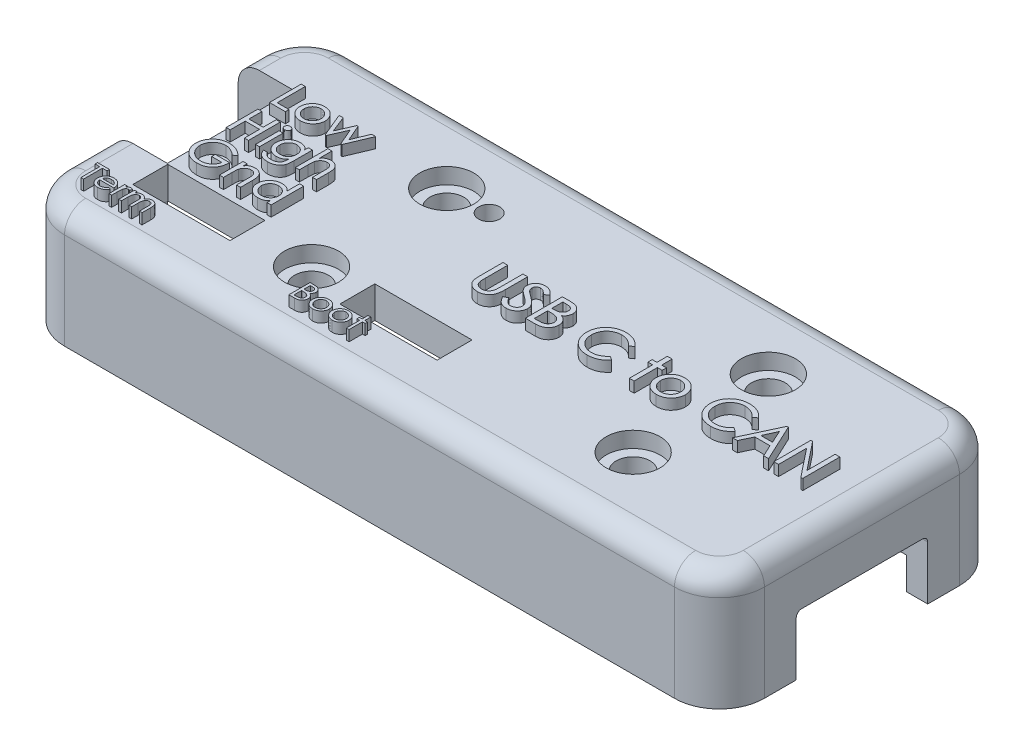
SolidWorks part; units mm, degrees
ref_plane "Front Plane" through (0, 0, 0) normal (0, 0, 1) x (1, 0, 0)
ref_plane "Top Plane" through (0, 0, 0) normal (0, 1, 0) x (1, 0, 0)
ref_plane "Right Plane" through (0, 0, 0) normal (1, 0, 0) x (0, 0, -1)
sketch "Sketch1" plane through (0, 0, 0) normal (0, 1, 0) x (1, 0, 0)
  line L0 (-0.25, 0.25) -> (55.35, 0.25)
  line L1 (0, 0) -> (55.1, 0)
  line L2 (0, 0) -> (0, -15.92)
  line L3 (0, -15.92) -> (55.1, -15.92)
  line L4 (55.1, 0) -> (55.1, -15.92)
  line L5 (55.35, 0.25) -> (55.35, -16.17)
  line L6 (-0.25, -16.17) -> (55.35, -16.17)
  line L7 (-0.25, 0.25) -> (-0.25, -16.17)
  line L8 (-1.25, 3.25) -> (56.35, 3.25)
  line L9 (58.35, 1.25) -> (58.35, -17.17)
  line L10 (-1.25, -19.17) -> (56.35, -19.17)
  line L11 (-3.25, 1.25) -> (-3.25, -17.17)
  line L12 (-3.25, -19.17) -> (58.35, -19.17) construction
  line L13 (-3.25, 3.25) -> (-3.25, -19.17) construction
  line L14 (58.35, 3.25) -> (58.35, -19.17) construction
  line L15 (-3.25, 3.25) -> (58.35, 3.25) construction
  line L20 (-1.25, -19.42) -> (56.35, -19.42)
  line L21 (58.6, 1.25) -> (58.6, -17.17)
  line L22 (-1.25, 3.5) -> (56.35, 3.5)
  line L23 (-3.5, 1.25) -> (-3.5, -17.17)
  line L24 (-1.25, -21.42) -> (56.35, -21.42)
  line L25 (60.6, 1.25) -> (60.6, -17.17)
  line L26 (-1.25, 5.5) -> (56.35, 5.5)
  line L27 (-5.5, 1.25) -> (-5.5, -17.17)
  circle A0 centre (45.375, -1.575) radius 1.6
  circle A1 centre (45.375, -14.345) radius 1.6
  circle A2 centre (15.005, -1.575) radius 1.6
  circle A3 centre (15.005, -14.345) radius 1.6
  arc A8 (-1.25, -19.17) -> (-3.25, -17.17) centre (-1.25, -17.17) cw
  arc A9 (58.35, -17.17) -> (56.35, -19.17) centre (56.35, -17.17) cw
  arc A10 (56.35, 3.25) -> (58.35, 1.25) centre (56.35, 1.25) cw
  arc A11 (-1.25, 3.25) -> (-3.25, 1.25) centre (-1.25, 1.25) ccw
  arc A16 (58.6, -17.17) -> (56.35, -19.42) centre (56.35, -17.17) cw
  arc A17 (56.35, 3.5) -> (58.6, 1.25) centre (56.35, 1.25) cw
  arc A18 (-1.25, 3.5) -> (-3.5, 1.25) centre (-1.25, 1.25) ccw
  arc A19 (-1.25, -19.42) -> (-3.5, -17.17) centre (-1.25, -17.17) cw
  arc A20 (60.6, -17.17) -> (56.35, -21.42) centre (56.35, -17.17) cw
  arc A21 (56.35, 5.5) -> (60.6, 1.25) centre (56.35, 1.25) cw
  arc A22 (-1.25, 5.5) -> (-5.5, 1.25) centre (-1.25, 1.25) ccw
  arc A23 (-1.25, -21.42) -> (-5.5, -17.17) centre (-1.25, -17.17) cw
  dimension "D8" = 3.2
  dimension "D9" = 3.2
  dimension "D10" = 3.2
  dimension "D11" = 3.2
  dimension "D15" = 2
  dimension "D1" = 15.92
  dimension "D2" = 55.1
  dimension "D4" = 9.725
  dimension "D5" = 30.37
  dimension "D6" = 12.77
  dimension "D7" = 1.575
  dimension "D3" = 0.25
  dimension "D14" = 3
  dimension "D16" = 0.25
  dimension "D17" = 2
extrude "Boss-Extrude4" add sketch "Sketch1" against normal blind 3 contours A23 L24 A20 L25 A21 L26 A22 L27 L20 A19 L23 A18 L22 A17 L21 A16 region at (-3.7505, 0, 19.6705)
extrude "Boss-Extrude5" add sketch "Sketch1<8>" along normal blind 5.1 contours A23 L24 A20 L25 A21 L26 A22 L27 L20 A19 L23 A18 L22 A17 L21 A16 | A19 L20 A16 L21 A17 L22 A18 L23 A11 L8 A10 L9 A9 L10 A8 L11 | L8 A11 L11 A8 L10 A9 L9 A10 L6 L7 L0 L5 region at (27.55, 0, -2.5945) region at (-2.7942, 0, 18.7142) region at (-3.7505, 0, 19.6705)
sketch "Sketch1<8>" plane through (0, 0, 0) normal (0, 1, 0) x (1, 0, 0) same geometry as "Sketch1"
extrude "Boss-Extrude6" add sketch "Sketch1<9>" along normal blind 3 from surface contours A20 L24 A23 L27 A22 L26 A21 L25 starting at face at (27.55, 5.1, 7.96)
sketch "Sketch1<9>" plane through (0, 0, 0) normal (0, 1, 0) x (1, 0, 0) same geometry as "Sketch1"
sketch "Sketch5" plane through (-5.5, 0, 0) normal (-1, 0, 0) x (0, 0, 1)
  line L0 (-1.25, -3) -> (-1.25, 8.1) construction
  line L1 (0.77, 8.1) -> (12.71, 8.1)
  line L2 (0.77, 8.1) -> (0.77, -3.76)
  line L3 (0.77, -3.76) -> (12.71, -3.76)
  line L4 (12.71, 8.1) -> (12.71, -3.76)
  line L5 (17.17, 8.1) -> (-1.25, 8.1) construction
  dimension "D1" = 2.02
  dimension "D2" = 11.94
  dimension "D3" = 11.86
  dimension "D4" = 0
extrude "Cut-Extrude4" cut sketch "Sketch5" against normal up to surface (5.25 mm away) up to face at (-0.25, 2.55, 7.96)
extrude "Cut-Extrude6" cut sketch "Sketch1<10>" along normal up to surface (8.1 mm away) contours L1 A0 | L1 A0 | L1 A2 | L3 A3 | L3 A3 | L3 A1 | L3 A1 | A2 region at (15.005, 0, 1.5769) region at (15.005, 0, 14.3431) region at (15.005, 0, 15.93) region at (45.375, 0, -0.01) region at (45.375, 0, 1.5769) region at (45.375, 0, 14.3431) region at (45.375, 0, 15.93) up to face at (17.4083, 8.1, 7.5533)
sketch "Sketch1<10>" plane through (0, 0, 0) normal (0, 1, 0) x (1, 0, 0) same geometry as "Sketch1"
sketch "Sketch6" plane through (0, 8.1, 0) normal (0, 1, 0) x (1, 0, 0)
  circle A0 centre (45.375, -14.345) radius 2.55
  circle A1 centre (45.375, -1.575) radius 2.55
  circle A2 centre (15.005, -1.575) radius 2.55
  circle A3 centre (15.005, -14.345) radius 2.55
  dimension "D1" = 5.1
  dimension "D2" = 5.1
  dimension "D3" = 5.1
  dimension "D4" = 5.1
extrude "Cut-Extrude7" cut sketch "Sketch6" against normal blind 1.5
sketch "Sketch9" plane through (0, 5.1, 0) normal (0, -1, 0) x (1, 0, 0)
  line L0 (-0.25, 16.17) -> (55.35, 16.17) construction
  line L1 (9.03, 12.77) -> (-0.15, 12.77)
  line L2 (9.03, 12.77) -> (9.03, 16.07)
  line L3 (9.03, 16.07) -> (-0.15, 16.07)
  line L4 (-0.15, 12.77) -> (-0.15, 16.07)
  line L5 (-0.25, 12.71) -> (-0.25, 16.17) construction
  line L7 (19.405, 12.77) -> (28.585, 12.77)
  line L8 (19.405, 12.77) -> (19.405, 16.07)
  line L9 (19.405, 16.07) -> (28.585, 16.07)
  line L10 (28.585, 12.77) -> (28.585, 16.07)
  circle A0 centre (15.005, 14.345) radius 1.6 construction
  dimension "D1" = 9.18
  dimension "D2" = 0.1
  dimension "D3" = 0.1
  dimension "D4" = 3.3
  dimension "D5" = 9.18
  dimension "D6" = 4.4
extrude "Cut-Extrude14" cut sketch "Sketch9" against normal blind 4
fillet "Fillet1" radius 2 9 edges at (-5.5, 8.1, 14.94) (-4.2552, 8.1, 20.1752) (27.55, 8.1, 21.42) (59.3552, 8.1, 20.1752) (60.6, 8.1, 7.96) (59.3552, 8.1, -4.2552) (-5.5, 8.1, -0.24) (-4.2552, 8.1, -4.2552) (27.55, 8.1, -5.5)
sketch "Sketch10" plane through (60.6, 0, 0) normal (1, 0, 0) x (0, 0, -1)
  line L1 (-13.6679, 2.57) -> (-2.2479, 2.57)
  line L2 (-14.1679, 2.07) -> (-14.1679, -3.93)
  line L3 (-13.6679, -4.43) -> (-2.2479, -4.43)
  line L4 (-1.7479, 2.07) -> (-1.7479, -3.93)
  line L5 (-17.17, -3) -> (-17.17, 6.1) construction
  line L6 (1.25, 6.1) -> (-17.17, 6.1) construction
  arc A0 (-14.1679, -3.93) -> (-13.6679, -4.43) centre (-13.6679, -3.93) ccw
  arc A1 (-2.2479, -4.43) -> (-1.7479, -3.93) centre (-2.2479, -3.93) ccw
  arc A2 (-2.2479, 2.57) -> (-1.7479, 2.07) centre (-2.2479, 2.07) cw
  arc A3 (-13.6679, 2.57) -> (-14.1679, 2.07) centre (-13.6679, 2.07) ccw
  point P8 (-1.7479, -4.43)
  point P11 (-1.7479, 2.57)
  point P14 (-14.1679, 2.57)
  dimension "D3" = 0.5
  dimension "D1" = 12.42
  dimension "D2" = 7
  dimension "D4" = 3.0021
  dimension "D5" = 3.53
extrude "Cut-Extrude15" cut sketch "Sketch10" against normal up to surface (5.25 mm away) up to face at (55.35, 2.55, 7.96)
sketch "Sketch11" plane through (0, 8.1, 0) normal (0, 1, 0) x (1, 0, 0)
  arc A0 (-3.5, -17.17) -> (-1.25, -19.42) centre (-1.25, -17.17) ccw construction
  text T0 "<b>Low</b>" font "Century Gothic" height 3
  text T1 "<b>High</b>" font "Century Gothic" height 3
  text T2 "<b>Gnd</b>" font "Century Gothic" height 3
  text T3 "<b>Term</b>" font "Century Gothic" height 2
  text T4 "<b>Boot</b>" font "Century Gothic" height 2
  text T5 "<b>USB C to CAN</b>"
extrude "Boss-Extrude7" add sketch "Sketch11" along normal blind 1
sketch "Sketch12" plane through (0, 8.1, 0) normal (0, 1, 0) x (1, 0, 0)
  circle A0 centre (15.005, -14.345) radius 2.5
  circle A1 centre (45.375, -14.345) radius 2.5
  circle A2 centre (45.375, -1.575) radius 2.5
  circle A3 centre (15.005, -1.575) radius 2.5
  dimension "D1" = 5
  dimension "D2" = 5
  dimension "D3" = 5
  dimension "D4" = 5
extrude "Cut-Extrude16" cut sketch "Sketch12" against normal up to surface (8.1 mm away) from surface up to face at (27.55, 0, 16.0208) starting at face at (4.44, 5.1, 14.42)
sketch "Sketch13" plane through (0, 8.1, 0) normal (0, 1, 0) x (1, 0, 0)
  circle A0 centre (19.005, -1.575) radius 1
  circle A1 centre (15.005, -1.575) radius 2.55 construction
  point P2 (0, 0)
  point P3 (0, 0)
  point P4 (0, 0)
  dimension "D1" = 2
  dimension "D2" = 4
extrude "Cut-Extrude17" cut sketch "Sketch13" against normal through all
